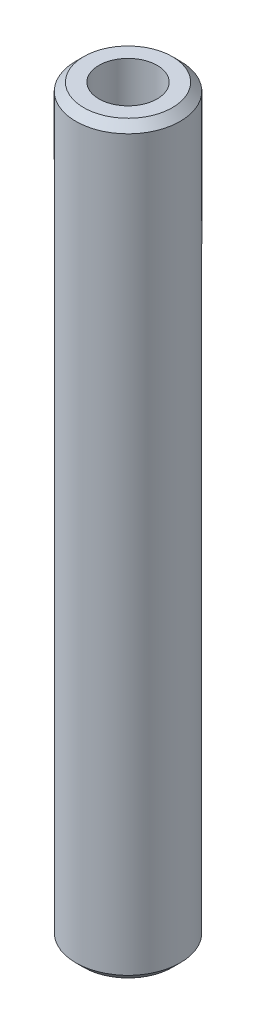
SolidWorks part; units mm, degrees
ref_plane "Front Plane" through (0, 0, 0) normal (0, 0, 1) x (1, 0, 0)
ref_plane "Top Plane" through (0, 0, 0) normal (0, 1, 0) x (1, 0, 0)
ref_plane "Right Plane" through (0, 0, 0) normal (1, 0, 0) x (0, 0, -1)
sketch "Sketch1" plane through (0, 0, 0) normal (0, 1, 0) x (1, 0, 0)
  circle A0 centre (0, 0) radius 10
  dimension "SHAFT_OD" = 20
extrude "Boss-Extrude1" add sketch "Sketch1" along normal blind 142.6727
sketch "Sketch2" plane through (0, 0, 0) normal (0, 1, 0) x (1, 0, 0)
  circle A0 centre (0, 0) radius 5.5813
  dimension "BORE_D" = 11.1626
extrude "Cut-Extrude1" cut sketch "Sketch2" along normal through all
chamfer "Chamfer1" distance 1.5137 angle 45 2 edges at (0, 142.6727, 10) (0, 0, 10)
